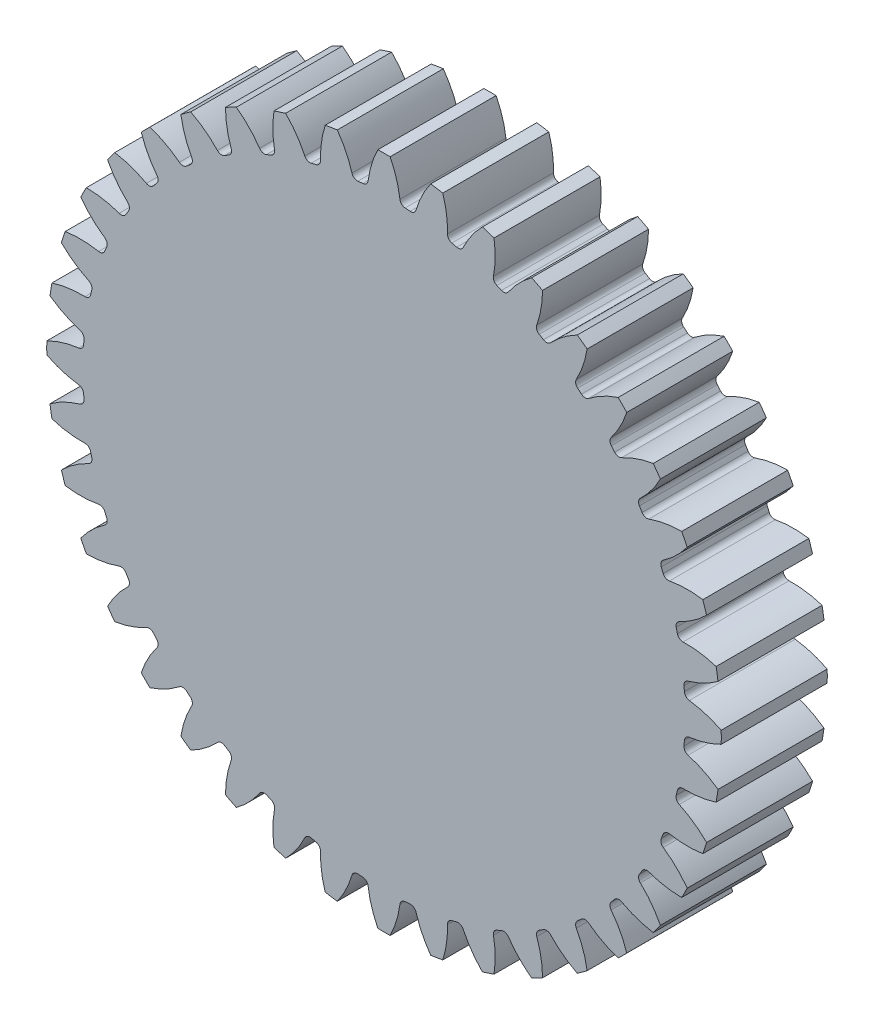
SolidWorks part; units mm, degrees
material "ABS"
ref_plane "Plane1" through (0, 0, 0) normal (0, 0, 1) x (1, 0, 0)
ref_plane "Plane2" through (0, 0, 0) normal (0, 1, 0) x (1, 0, 0)
ref_plane "Plane3" through (0, 0, 0) normal (1, 0, 0) x (0, 0, -1)
sketch "Esquisse1" plane through (0, 0, 0) normal (0, 0, 1) x (1, 0, 0)
  circle A0 centre (0, 0) radius 1.15
  dimension "D1" = 2.3
extrude "Base-Extrusion" add sketch "Esquisse1" along normal blind 2.5
sketch "Parametres" plane through (0, 0, 2.5) normal (0, 0, 1) x (1, 0, 0)
  line L0 (-33.4711, 41.7411) -> (6.5289, 41.7411)
  line L1 (-33.4711, 34.0759) -> (-32.9711, 34.0759)
  line L2 (-33.4711, 23.0892) -> (-13.4711, 23.0892)
  line L3 (-33.4711, -2.6579) -> (-33.1221, -2.6579)
  line L4 (-38.9094, -12.5583) -> (-35.7678, -12.5583)
  line L5 (-48.8826, -19.2556) -> (-38.8826, -19.2556)
  line L6 (-48.8826, -29.9283) -> (-38.3826, -29.9283)
  line L7 (-48.8826, -38.2322) -> (-39.5076, -38.2322)
  line L8 (-48.8826, -45.1309) -> (-39.4856, -45.1309)
  line L9 (-48.8826, -60.7647) -> (-48.0972, -60.7647)
  line L10 (-48.8826, -76.1039) -> (-47.8644, -76.1039)
  line L11 (-48.8826, -88.0795) -> (-48.4201, -88.0795)
  line L12 (-48.8826, -98.8973) -> (-48.5022, -98.8973)
  line L13 (16.9123, -61.9871) -> (21.4123, -61.9871)
  line L14 (18.5152, -81.0212) -> (24.7231, -81.0212)
  line L15 (18.5152, -96.0481) -> (20.5906, -96.0481)
  line L16 (-33.4711, 13.8609) -> (-26.8711, 13.8609)
  dimension "Z" = 40
  dimension "m" = 0.5
  dimension "Alpha" = 20
  dimension "Alpha_rad" = 0.3491
  dimension "PI" = 3.1416
  dimension "R" = 10
  dimension "RT" = 10.5
  dimension "RP" = 9.375
  dimension "Rb" = 9.3969
  dimension "E" = 0.7854
  dimension "Eb" = 1.0181
  dimension "As" = 0.4625
  dimension "Et" = 0.3803
  dimension "Ap" = 4.5
  dimension "Ab" = 6.2079
  dimension "At" = 2.0754
  dimension "k" = 6.6
sketch "Esquisse3" plane through (0, 0, 0) normal (0, 0, 1) x (1, 0, 0)
  line L0 (0, 0) -> (0, 29.3764) construction
  line L1 (-0.7356, 9.3461) -> (0, 0)
  line L2 (0, 0) -> (0.7356, 9.3461)
  line L3 (0, 0) -> (0.5088, 9.3831) construction
  line L4 (0, 0) -> (0.1902, 10.4983) construction
  line L5 (0, 0) -> (0.3926, 9.9923) construction
  arc A0 (0.1902, 10.4983) -> (0.5107, 9.3611) centre (-2.5179, 9.1213) cw
  arc A1 (-0.1902, 10.4983) -> (-0.5107, 9.3611) centre (2.5179, 9.1213) ccw
  arc A2 (0.7356, 9.3461) -> (0.5107, 9.3611) centre (0, 0) ccw
  arc A3 (-0.7356, 9.3461) -> (-0.5107, 9.3611) centre (0, 0) cw
  arc A4 (0.1902, 10.4983) -> (-0.1902, 10.4983) centre (0, 0) ccw
  dimension "D7" = 1.038
  dimension "D1" = 10.5
  dimension "D2" = 3.104
  dimension "D3" = 2.25
  dimension "D4" = 9
  dimension "D5" = 9.3969
  dimension "D6" = 10
  dimension "D8" = 9.375
extrude "Boss.-Extru.1" add sketch "Esquisse3" along normal blind 3.3
fillet "Congé1" radius 0.175 2 edges at (0.5107, 9.3611, 1.65) (-0.5107, 9.3611, 1.65)
ref_axis "Axe1" through (0, 0, 53.3) along (0, 0, -1)
pattern_circular "Répétition circulaire4" count 40 every 9 about axis through (0, 0, 53.3) along (0, 0, -1) of "Boss.-Extru.1", "Congé1"
equation "\"PI@Parametres\" = 3.141592654"
equation "\"Alpha_rad@Parametres\" = \"Alpha@Parametres\"*\"PI@Parametres\"/180"
equation "\"R@Parametres\" = \"Z@Parametres\"*\"m@Parametres\"/2"
equation "\"RT@Parametres\" = \"R@Parametres\"+\"m@Parametres\""
equation "\"RP@Parametres\" = \"R@Parametres\"-1.25*\"m@Parametres\""
equation "\"Rb@Parametres\" = \"R@Parametres\"*cos(\"Alpha_rad@Parametres\")"
equation "\"E@Parametres\" = \"PI@Parametres\"*\"R@Parametres\"/\"Z@Parametres\""
equation "\"Eb@Parametres\" = \"Rb@Parametres\"*((\"PI@Parametres\"*\"m@Parametres\"/(2*\"R@Parametres\"))+2*(tan(\"Alpha_rad@Parametres\")-\"Alpha_rad@Parametres\"))"
equation "\"As@Parametres\" = atn(sqr(\"RT@Parametres\"*\"RT@Parametres\"-\"Rb@Parametres\"*\"Rb@Parametres\")/\"Rb@Parametres\")"
equation "\"Et@Parametres\" = \"RT@Parametres\"*((\"E@Parametres\"/\"R@Parametres\")+2*(tan(\"Alpha_rad@Parametres\")-\"Alpha_rad@Parametres\"-tan(\"As@Parametres\")+\"As@Parametres\"))"
equation "\"Ap@Parametres\" = (\"E@Parametres\"/\"R@Parametres\")*180/\"PI@Parametres\""
equation "\"Ab@Parametres\" = (\"Eb@Parametres\"/\"Rb@Parametres\")*180/\"PI@Parametres\""
equation "\"At@Parametres\" = (\"Et@Parametres\"/\"RT@Parametres\")*180/\"PI@Parametres\""
equation "\"D7@Esquisse3\" = \"At@Parametres\"/2"
equation "\"D3@Esquisse3\"=\"Ap@Parametres\"/2"
equation "\"D2@Esquisse3\"=\"Ab@Parametres\"/2"
equation "\"D5@Esquisse3\"=\"Rb@Parametres\""
equation "\"D6@Esquisse3\"=\"R@Parametres\""
equation "\"D1@Esquisse3\"=\"RT@Parametres\""
equation "\"D4@Esquisse3\" = \"Ap@Parametres\"*2"
equation "\"D1@Boss.-Extru.1\" = \"k@Parametres\"*\"m@Parametres\""
equation "\"D1@Congé1\" = 0.35*\"m@Parametres\""
equation "\"D2@Répétition circulaire4\" = \"Ap@Parametres\"*2"
equation "\"D1@Répétition circulaire4\" = \"Z@Parametres\""
equation "\"D8@Esquisse3\" = \"RP@Parametres\""
